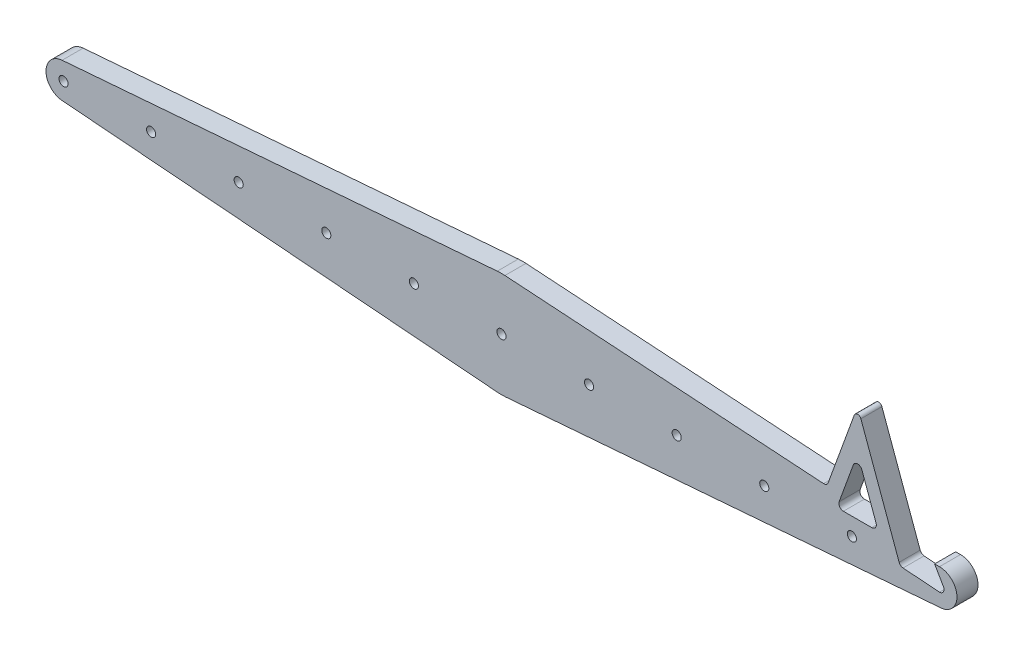
SolidWorks part; units mm, degrees
material "Pine"
ref_plane "Front Plane" through (0, 0, 0) normal (0, 0, 1) x (1, 0, 0)
ref_plane "Top Plane" through (0, 0, 0) normal (0, 1, 0) x (1, 0, 0)
ref_plane "Right Plane" through (0, 0, 0) normal (1, 0, 0) x (0, 0, -1)
sketch "Sketch1" plane through (0, 0, 0) normal (0, 0, 1) x (1, 0, 0)
  line L0 (0, 5) -> (250, 5)
  line L1 (250, -5) -> (0, -5)
  circle A0 centre (0, 0) radius 5
  circle A1 centre (250, 0) radius 5
  dimension "D1" = 250
  dimension "D2" = 10
extrude "Boss-Extrude1" add sketch "Sketch1" along normal blind 6 contours A1 L0 A0 L1 | A1 | A0 region at (125, 0, 0) region at (0, 0, 0) region at (250, 0, 0)
ref_plane "Plane1" through (0, 0, 3) normal (0, 0, 1) x (1, 0, 0)
sketch "Sketch2" plane through (0, 0, 6) normal (0, 0, 1) x (1, 0, 0)
  circle A0 centre (0, 0) radius 1.3
  circle A1 centre (250, 0) radius 1.3
  dimension "D1" = 2.6
extrude "Cut-Extrude1" cut sketch "Sketch2" against normal through all
pattern_linear "LPattern1" count 10 spacing 25 along (1, 0, 0) of "Cut-Extrude1"
sketch "Sketch3" plane through (0, 0, 6) normal (0, 0, 1) x (1, 0, 0)
  line L0 (251.1258, 0.65) -> (248.6144, 5)
  line L1 (0, 5) -> (250, 5) construction
  line L2 (250, 0) -> (225, 0) construction
  line L3 (248.6144, 5) -> (236.7967, 5)
  line L4 (225.6936, 30.342) -> (216.4699, 5)
  line L5 (250, -1.3) -> (240, -1.3)
  line L6 (238.7784, -0.4446) -> (227.573, 30.342)
  line L7 (216.4699, 5) -> (236.7967, 5)
  circle A0 centre (250, 0) radius 1.3 construction
  circle A1 centre (250, 0) radius 1.3
  arc A2 (227.573, 30.342) -> (225.6936, 30.342) centre (226.6333, 30) ccw
  arc A4 (240, -1.3) -> (238.7784, -0.4446) centre (240, 0) cw
  circle M17 centre (250, 0) radius 1.3
  line M20 (250, 5) -> (0, 5)
  dimension "D3" = 1
  dimension "D6" = 1.3
  dimension "D1" = 300
  dimension "D2" = 70
  dimension "D4" = 25
  dimension "D5" = 70
  dimension "D7" = 10
extrude "Cut-Extrude3" cut sketch "Sketch3" against normal through all contours L2 A1 L0 L6 M20 | L2 L6 A4 L5 M17 | A1 M17 | L0 L3 L7 L4 A2 L6 A4 L5 region at (243.6192, 2.5517, 6) region at (251.2202, 0.3269, 6) region at (243.9739, -0.6495, 6)
extrude "Boss-Extrude2" add sketch "Sketch3<4>" against normal through all contours L6 A2 L4 M20 region at (226.6333, 14.2147, 6)
sketch "Sketch3<4>" plane through (0, 0, 6) normal (0, 0, 1) x (1, 0, 0) same geometry as "Sketch3"
sketch "Sketch4" plane through (0, 0, 6) normal (0, 0, 1) x (1, 0, 0)
  line L0 (0, 5) -> (216.4699, 5) construction
  line L5 (229.4524, 28.9739) -> (220.2286, 3.6319)
  line L6 (225.4117, 17.8723) -> (221.3616, 6.7446)
  line L7 (222.5832, 5) -> (230.6834, 5)
  line L8 (235.0196, -1.8127) -> (223.8142, 28.9739)
  line L9 (231.905, 6.7446) -> (227.8549, 17.8723)
  arc A0 (230.6834, 5) -> (231.905, 6.7446) centre (230.6834, 6.3) ccw
  arc A1 (221.3616, 6.7446) -> (222.5832, 5) centre (222.5832, 6.3) ccw
  arc A2 (227.8549, 17.8723) -> (225.4117, 17.8723) centre (226.6333, 17.4276) ccw
  dimension "D3" = 1.3
  dimension "D1" = 4
  dimension "D2" = 4
extrude "Cut-Extrude4" cut sketch "Sketch4" against normal through all
sketch "Sketch5" plane through (0, 0, 6) normal (0, 0, 1) x (1, 0, 0)
  line L0 (123.8, 14.9519) -> (-0.4, 4.984)
  line L1 (123.8, -14.9519) -> (-0.4, -4.984)
  line L2 (250.4, -4.984) -> (126.2, -14.9519)
  line L3 (250, -1.3) -> (239.6144, -0.5084)
  line L4 (125.9822, 14.9678) -> (216.9293, 9)
  line L5 (225.6936, 30.342) -> (216.4699, 5) construction
  line L7 (250, -1.3) -> (240, -1.3) construction
  line L8 (250, -1.3) -> (240, -1.3)
  line L9 (238.7784, -0.4446) -> (227.573, 30.342) construction
  line L10 (238.4916, 0.3433) -> (227.573, 30.342)
  line L11 (225.6936, 30.342) -> (218.236, 9.8526)
  line L12 (0, 5) -> (216.4699, 5) construction
  line L13 (0, 5) -> (216.4699, 5)
  line L14 (250, -5) -> (0, -5) construction
  line L15 (250, -5) -> (0, -5)
  circle A0 centre (125, 0) radius 15
  arc A1 (0, 5) -> (0, -5) centre (0, 0) ccw construction
  arc A2 (250, -5) -> (250, 5) centre (250, 0) ccw construction
  arc A3 (238.7784, -0.4446) -> (240, -1.3) centre (240, 0) ccw construction
  arc A4 (238.7784, -0.4446) -> (240, -1.3) centre (240, 0) ccw
  arc A6 (238.4916, 0.3433) -> (239.6144, -0.5084) centre (239.7132, 0.7879) ccw
  arc A7 (218.236, 9.8526) -> (216.9293, 9) centre (217.0144, 10.2972) cw
  arc A8 (0, 5) -> (0, -5) centre (0, 0) ccw
  arc A9 (250, -5) -> (250, 5) centre (250, 0) ccw
  point P32 (0, 0)
  line M20 (250, -1.3) -> (240, -1.3)
  arc M21 (240, -1.3) -> (238.7784, -0.4446) centre (240, 0) cw
  line M22 (238.7784, -0.4446) -> (227.573, 30.342)
  line M24 (225.6936, 30.342) -> (216.4699, 5)
  line M25 (216.4699, 5) -> (0, 5)
  arc M26 (0, 5) -> (0, -5) centre (0, 0) ccw
  line M27 (0, -5) -> (250, -5)
  arc M28 (250, -5) -> (250, 5) centre (250, 0) ccw
  dimension "D1" = 30
  dimension "D3" = 1.3
  dimension "D2" = 1.3
  dimension "D4" = 4
extrude "Boss-Extrude3" add sketch "Sketch5" against normal through all contours A0 L0 M26 M25 | A0 L1 M27 M26 | L13 A0 | L15 A0 | A0 L2 M28 M27 | A7 L4 A0 M24 M25 | A6 L3 M22 M21 M20 region at (76.19, 8.1937, 6) region at (125, 9.1422, 6) region at (170.902, 8.645, 6) region at (76.19, -8.1937, 6) region at (125, -9.1422, 6) region at (173.81, -8.1937, 6) region at (242.6356, -0.9925, 6)
